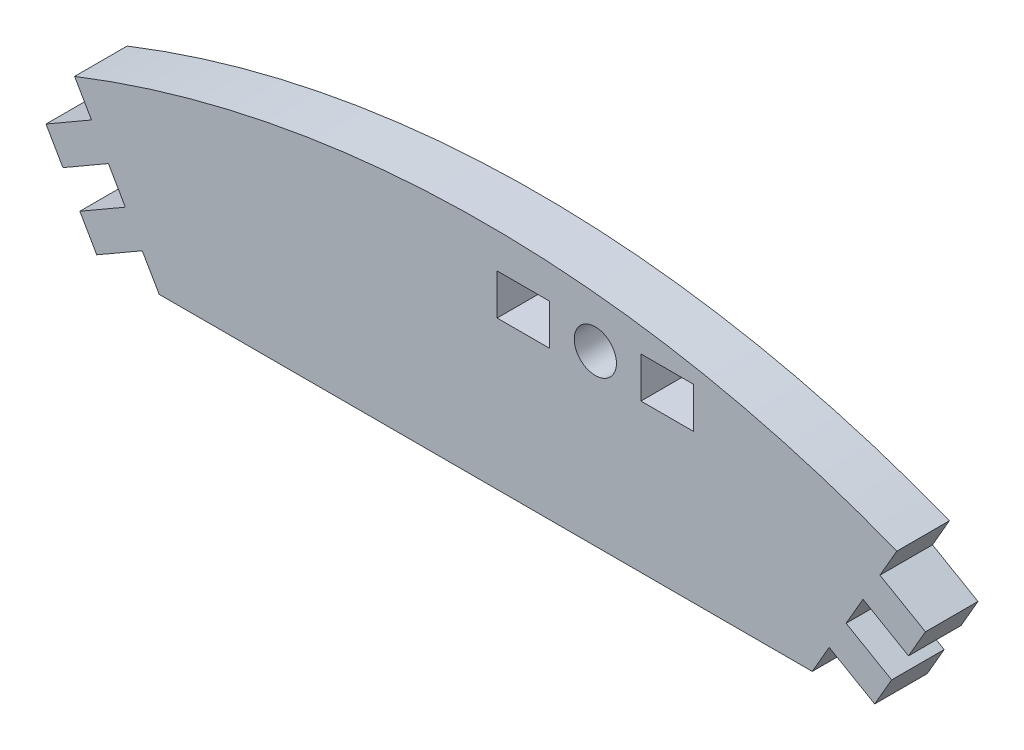
SolidWorks part; units mm, degrees
ref_plane "Front Plane" through (0, 0, 0) normal (0, 0, 1) x (1, 0, 0)
ref_plane "Top Plane" through (0, 0, 0) normal (0, 1, 0) x (1, 0, 0)
ref_plane "Right Plane" through (0, 0, 0) normal (1, 0, 0) x (0, 0, -1)
sketch "Sketch1" plane through (0, 0, 0) normal (0, 0, 1) x (1, 0, 0)
  line L1 (-32, 88) -> (32, 88)
  line L2 (-38.6309, 99.4851) -> (-40.2886, 102.3564)
  line L3 (0, 88) -> (0, 136.6413) construction
  line L5 (32, 88) -> (33.6577, 90.8713)
  line L6 (33.6577, 90.8713) -> (38.1178, 88.2963)
  line L7 (38.1178, 88.2963) -> (39.7755, 91.1675)
  line L8 (39.7755, 91.1675) -> (35.3155, 93.7425)
  line L9 (35.3155, 93.7425) -> (36.9732, 96.6138)
  line L10 (36.9732, 96.6138) -> (41.4332, 94.0388)
  line L11 (41.4332, 94.0388) -> (43.091, 96.9101)
  line L12 (43.091, 96.9101) -> (38.6309, 99.4851)
  line L13 (38.6309, 99.4851) -> (40.2886, 102.3564)
  line L14 (-43.091, 96.9101) -> (-38.6309, 99.4851)
  line L15 (-41.4332, 94.0388) -> (-43.091, 96.9101)
  line L16 (-36.9732, 96.6138) -> (-41.4332, 94.0388)
  line L17 (-35.3155, 93.7425) -> (-36.9732, 96.6138)
  line L18 (-39.7755, 91.1675) -> (-35.3155, 93.7425)
  line L19 (-38.1178, 88.2963) -> (-39.7755, 91.1675)
  line L20 (-33.6577, 90.8713) -> (-38.1178, 88.2963)
  line L21 (-32, 88) -> (-33.6577, 90.8713)
  arc A0 (-40.2886, 102.3564) -> (40.2886, 102.3564) centre (0, 0) cw
  point P12 (0, 110)
  dimension "D1" = 110
  dimension "D2" = 22
  dimension "D3" = 120
  dimension "D4" = 64
  dimension "D5" = 5.15
extrude "Boss-Extrude1" add sketch "Sketch1" along normal blind 5.15
sketch "Sketch2" plane through (0, 0, 5.15) normal (0, 0, 1) x (1, 0, 0)
  line L0 (2.7783, 102) -> (40.0829, 102) construction
  line L1 (0, 138.9207) -> (0, 64.2148) construction
  line L2 (0, -55) -> (0, 55) construction
  line L3 (0, 92.1138) -> (7.9, 92.1138) construction
  line L4 (2.7783, 88) -> (2.7783, 102) construction
  line L5 (7.9, 92.1138) -> (-24.7172, 92.1138) construction
  line L6 (-32, 88) -> (32, 88) construction
  line L7 (15.2118, 104.5506) -> (6.2682, 104.5506) construction
  line L9 (15.2118, 106.5506) -> (20.3618, 106.5506)
  line L10 (15.2118, 106.5506) -> (15.2118, 102.5506)
  line L11 (15.2118, 102.5506) -> (20.3618, 102.5506)
  line L12 (20.3618, 106.5506) -> (20.3618, 102.5506)
  line L13 (1.1182, 106.5506) -> (6.2682, 106.5506)
  line L14 (1.1182, 106.5506) -> (1.1182, 102.5506)
  line L15 (1.1182, 102.5506) -> (6.2682, 102.5506)
  line L16 (6.2682, 106.5506) -> (6.2682, 102.5506)
  circle A0 centre (10.74, 104.5506) radius 2.0675
  point P27 (10.74, 104.5506)
  dimension "D1" = 10.74
  dimension "D2" = 4.135
  dimension "D3" = 7.9
  dimension "D4" = 14
  dimension "D5" = 5.15
  dimension "D6" = 4
  dimension "D7" = 1.1182
extrude "Cut-Extrude1" cut sketch "Sketch2" against normal through all
